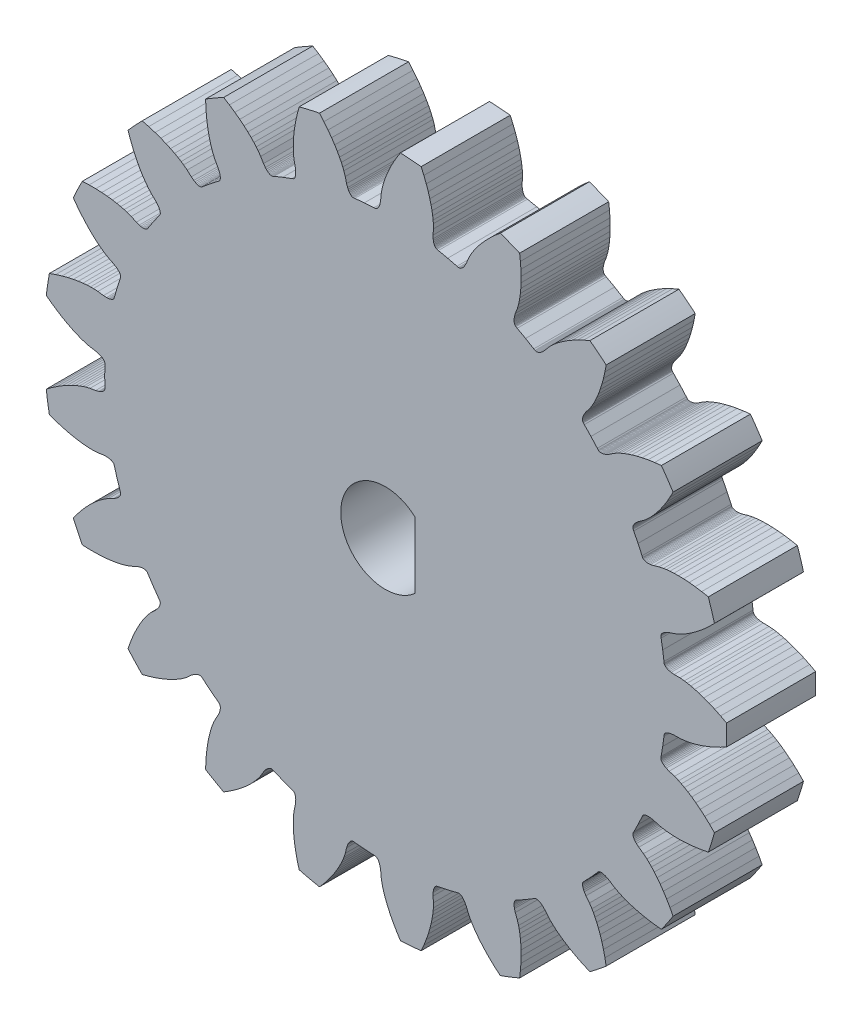
SolidWorks part; units mm, degrees
ref_plane "Front Plane" through (0, 0, 0) normal (0, 0, 1) x (1, 0, 0)
ref_plane "Top Plane" through (0, 0, 0) normal (0, 1, 0) x (1, 0, 0)
ref_plane "Right Plane" through (0, 0, 0) normal (1, 0, 0) x (0, 0, -1)
sketch "Model" plane through (0, 0, 0) normal (0, 0, 1) x (1, 0, 0)
  line L0 (10.9267, 2.8918) -> (10.7633, 2.7404)
  line L1 (10.7633, 2.7404) -> (10.6079, 2.6079)
  line L2 (10.6079, 2.6079) -> (10.4602, 2.4924)
  line L3 (10.4602, 2.4924) -> (10.3215, 2.3929)
  line L4 (10.3215, 2.3929) -> (10.1944, 2.3095)
  line L5 (10.1944, 2.3095) -> (10.0772, 2.2395)
  line L6 (10.0772, 2.2395) -> (9.9721, 2.1826)
  line L7 (9.9721, 2.1826) -> (9.8817, 2.1384)
  line L8 (9.8817, 2.1384) -> (9.7426, 2.0805)
  line L9 (9.7426, 2.0805) -> (9.5615, 2.023)
  line L10 (9.5615, 2.023) -> (9.4651, 1.9818)
  line L11 (9.4651, 1.9818) -> (9.4245, 1.9597)
  line L12 (9.4245, 1.9597) -> (9.3889, 1.9369)
  line L13 (9.3889, 1.9369) -> (9.3585, 1.9135)
  line L14 (9.3585, 1.9135) -> (9.3331, 1.8898)
  line L15 (9.3331, 1.8898) -> (9.3128, 1.866)
  line L16 (9.3128, 1.866) -> (9.2976, 1.8422)
  line L17 (9.2976, 1.8422) -> (9.2875, 1.8187)
  line L18 (9.2875, 1.8187) -> (9.2824, 1.7958)
  line L19 (9.2824, 1.7958) -> (9.2824, 1.7734)
  line L20 (9.2824, 1.7734) -> (9.291, 1.7262)
  line L21 (9.291, 1.7262) -> (9.3445, 1.4084)
  line L22 (9.3445, 1.4084) -> (9.3871, 1.0891)
  line L23 (9.3871, 1.0891) -> (9.3927, 1.0414)
  line L24 (9.3927, 1.0414) -> (9.3994, 1.0201)
  line L25 (9.3994, 1.0201) -> (9.411, 0.9996)
  line L26 (9.411, 0.9996) -> (9.4276, 0.9802)
  line L27 (9.4276, 0.9802) -> (9.4491, 0.9619)
  line L28 (9.4491, 0.9619) -> (9.4755, 0.9451)
  line L29 (9.4755, 0.9451) -> (9.5067, 0.93)
  line L30 (9.5067, 0.93) -> (9.5427, 0.9166)
  line L31 (9.5427, 0.9166) -> (9.5834, 0.9053)
  line L32 (9.5834, 0.9053) -> (9.6287, 0.8961)
  line L33 (9.6287, 0.8961) -> (9.733, 0.8852)
  line L34 (9.733, 0.8852) -> (9.923, 0.8836)
  line L35 (9.923, 0.8836) -> (10.073, 0.8693)
  line L36 (10.073, 0.8693) -> (10.1724, 0.8537)
  line L37 (10.1724, 0.8537) -> (10.2896, 0.8303)
  line L38 (10.2896, 0.8303) -> (10.4222, 0.7979)
  line L39 (10.4222, 0.7979) -> (10.5682, 0.7558)
  line L40 (10.5682, 0.7558) -> (10.7301, 0.7016)
  line L41 (10.7301, 0.7016) -> (10.9053, 0.6347)
  line L42 (10.9053, 0.6347) -> (11.0929, 0.5539)
  line L43 (11.0929, 0.5539) -> (11.2936, 0.4574)
  line L44 (11.2936, 0.4574) -> (11.4947, 0.3502)
  line L45 (11.4947, -0.3502) -> (11.2936, -0.4574)
  line L46 (11.2936, -0.4574) -> (11.0929, -0.5539)
  line L47 (11.0929, -0.5539) -> (10.9053, -0.6347)
  line L48 (10.9053, -0.6347) -> (10.7301, -0.7016)
  line L49 (10.7301, -0.7016) -> (10.5682, -0.7558)
  line L50 (10.5682, -0.7558) -> (10.4222, -0.7979)
  line L51 (10.4222, -0.7979) -> (10.2896, -0.8303)
  line L52 (10.2896, -0.8303) -> (10.1724, -0.8537)
  line L53 (10.1724, -0.8537) -> (10.073, -0.8693)
  line L54 (10.073, -0.8693) -> (9.923, -0.8836)
  line L55 (9.923, -0.8836) -> (9.733, -0.8852)
  line L56 (9.733, -0.8852) -> (9.6287, -0.8961)
  line L57 (9.6287, -0.8961) -> (9.5834, -0.9053)
  line L58 (9.5834, -0.9053) -> (9.5427, -0.9166)
  line L59 (9.5427, -0.9166) -> (9.5067, -0.93)
  line L60 (9.5067, -0.93) -> (9.4755, -0.9451)
  line L61 (9.4755, -0.9451) -> (9.4491, -0.9619)
  line L62 (9.4491, -0.9619) -> (9.4276, -0.9802)
  line L63 (9.4276, -0.9802) -> (9.411, -0.9996)
  line L64 (9.411, -0.9996) -> (9.3994, -1.0201)
  line L65 (9.3994, -1.0201) -> (9.3927, -1.0414)
  line L66 (9.3927, -1.0414) -> (9.3871, -1.0891)
  line L67 (9.3871, -1.0891) -> (9.3445, -1.4084)
  line L68 (9.3445, -1.4084) -> (9.291, -1.7262)
  line L69 (9.291, -1.7262) -> (9.2824, -1.7734)
  line L70 (9.2824, -1.7734) -> (9.2824, -1.7958)
  line L71 (9.2824, -1.7958) -> (9.2875, -1.8187)
  line L72 (9.2875, -1.8187) -> (9.2976, -1.8422)
  line L73 (9.2976, -1.8422) -> (9.3128, -1.866)
  line L74 (9.3128, -1.866) -> (9.3331, -1.8898)
  line L75 (9.3331, -1.8898) -> (9.3585, -1.9135)
  line L76 (9.3585, -1.9135) -> (9.3889, -1.9369)
  line L77 (9.3889, -1.9369) -> (9.4245, -1.9597)
  line L78 (9.4245, -1.9597) -> (9.4651, -1.9818)
  line L79 (9.4651, -1.9818) -> (9.5615, -2.023)
  line L80 (9.5615, -2.023) -> (9.7426, -2.0805)
  line L81 (9.7426, -2.0805) -> (9.8817, -2.1384)
  line L82 (9.8817, -2.1384) -> (9.9721, -2.1826)
  line L83 (9.9721, -2.1826) -> (10.0772, -2.2395)
  line L84 (10.0772, -2.2395) -> (10.1944, -2.3095)
  line L85 (10.1944, -2.3095) -> (10.3215, -2.3929)
  line L86 (10.3215, -2.3929) -> (10.4602, -2.4924)
  line L87 (10.4602, -2.4924) -> (10.6079, -2.6079)
  line L88 (10.6079, -2.6079) -> (10.7633, -2.7404)
  line L89 (10.7633, -2.7404) -> (10.9267, -2.8918)
  line L90 (10.9267, -2.8918) -> (11.0872, -3.0535)
  line L91 (10.8808, -3.7227) -> (10.657, -3.7659)
  line L92 (10.657, -3.7659) -> (10.4368, -3.799)
  line L93 (10.4368, -3.799) -> (10.2338, -3.8209)
  line L94 (10.2338, -3.8209) -> (10.0466, -3.8332)
  line L95 (10.0466, -3.8332) -> (9.8759, -3.8372)
  line L96 (9.8759, -3.8372) -> (9.724, -3.8345)
  line L97 (9.724, -3.8345) -> (9.5877, -3.8263)
  line L98 (9.5877, -3.8263) -> (9.4689, -3.8142)
  line L99 (9.4689, -3.8142) -> (9.3693, -3.7997)
  line L100 (9.3693, -3.7997) -> (9.2217, -3.7692)
  line L101 (9.2217, -3.7692) -> (9.0397, -3.7147)
  line L102 (9.0397, -3.7147) -> (8.9368, -3.6944)
  line L103 (8.9368, -3.6944) -> (8.8908, -3.6898)
  line L104 (8.8908, -3.6898) -> (8.8486, -3.6886)
  line L105 (8.8486, -3.6886) -> (8.8103, -3.6908)
  line L106 (8.8103, -3.6908) -> (8.7759, -3.6961)
  line L107 (8.7759, -3.6961) -> (8.7458, -3.7044)
  line L108 (8.7458, -3.7044) -> (8.7198, -3.7154)
  line L109 (8.7198, -3.7154) -> (8.6982, -3.7291)
  line L110 (8.6982, -3.7291) -> (8.6811, -3.7453)
  line L111 (8.6811, -3.7453) -> (8.6685, -3.7637)
  line L112 (8.6685, -3.7637) -> (8.649, -3.8076)
  line L113 (8.649, -3.8076) -> (8.5142, -4.1002)
  line L114 (8.5142, -4.1002) -> (8.3695, -4.3881)
  line L115 (8.3695, -4.3881) -> (8.3473, -4.4307)
  line L116 (8.3473, -4.4307) -> (8.3407, -4.452)
  line L117 (8.3407, -4.452) -> (8.3388, -4.4755)
  line L118 (8.3388, -4.4755) -> (8.3416, -4.5009)
  line L119 (8.3416, -4.5009) -> (8.3491, -4.5281)
  line L120 (8.3491, -4.5281) -> (8.3614, -4.5568)
  line L121 (8.3614, -4.5568) -> (8.3787, -4.587)
  line L122 (8.3787, -4.587) -> (8.4009, -4.6183)
  line L123 (8.4009, -4.6183) -> (8.4281, -4.6506)
  line L124 (8.4281, -4.6506) -> (8.4604, -4.6837)
  line L125 (8.4604, -4.6837) -> (8.5404, -4.7514)
  line L126 (8.5404, -4.7514) -> (8.6965, -4.8598)
  line L127 (8.6965, -4.8598) -> (8.8124, -4.9561)
  line L128 (8.8124, -4.9561) -> (8.8858, -5.025)
  line L129 (8.8858, -5.025) -> (8.9694, -5.1103)
  line L130 (8.9694, -5.1103) -> (9.0607, -5.2117)
  line L131 (9.0607, -5.2117) -> (9.1576, -5.3289)
  line L132 (9.1576, -5.3289) -> (9.2609, -5.4648)
  line L133 (9.2609, -5.4648) -> (9.3679, -5.6188)
  line L134 (9.3679, -5.6188) -> (9.4774, -5.7912)
  line L135 (9.4774, -5.7912) -> (9.5889, -5.984)
  line L136 (9.5889, -5.984) -> (9.6946, -6.1858)
  line L137 (9.3001, -6.7645) -> (9.0736, -6.7398)
  line L138 (9.0736, -6.7398) -> (8.8533, -6.7065)
  line L139 (8.8533, -6.7065) -> (8.6529, -6.6676)
  line L140 (8.6529, -6.6676) -> (8.4704, -6.6242)
  line L141 (8.4704, -6.6242) -> (8.3061, -6.5777)
  line L142 (8.3061, -6.5777) -> (8.1617, -6.5303)
  line L143 (8.1617, -6.5303) -> (8.0339, -6.4824)
  line L144 (8.0339, -6.4824) -> (7.9239, -6.4357)
  line L145 (7.9239, -6.4357) -> (7.833, -6.3926)
  line L146 (7.833, -6.3926) -> (7.701, -6.3199)
  line L147 (7.701, -6.3199) -> (7.5431, -6.2141)
  line L148 (7.5431, -6.2141) -> (7.4508, -6.1645)
  line L149 (7.4508, -6.1645) -> (7.4082, -6.1465)
  line L150 (7.4082, -6.1465) -> (7.3682, -6.1329)
  line L151 (7.3682, -6.1329) -> (7.331, -6.1237)
  line L152 (7.331, -6.1237) -> (7.2966, -6.1186)
  line L153 (7.2966, -6.1186) -> (7.2653, -6.1177)
  line L154 (7.2653, -6.1177) -> (7.2373, -6.1206)
  line L155 (7.2373, -6.1206) -> (7.2126, -6.1273)
  line L156 (7.2126, -6.1273) -> (7.1915, -6.1377)
  line L157 (7.1915, -6.1377) -> (7.174, -6.1515)
  line L158 (7.174, -6.1515) -> (7.1425, -6.1878)
  line L159 (7.1425, -6.1878) -> (6.9273, -6.4276)
  line L160 (6.9273, -6.4276) -> (6.7042, -6.6601)
  line L161 (6.7042, -6.6601) -> (6.6705, -6.6942)
  line L162 (6.6705, -6.6942) -> (6.6579, -6.7127)
  line L163 (6.6579, -6.7127) -> (6.6492, -6.7346)
  line L164 (6.6492, -6.7346) -> (6.6443, -6.7597)
  line L165 (6.6443, -6.7597) -> (6.6435, -6.7879)
  line L166 (6.6435, -6.7879) -> (6.6468, -6.819)
  line L167 (6.6468, -6.819) -> (6.6544, -6.8528)
  line L168 (6.6544, -6.8528) -> (6.6664, -6.8893)
  line L169 (6.6664, -6.8893) -> (6.6829, -6.9282)
  line L170 (6.6829, -6.9282) -> (6.704, -6.9693)
  line L171 (6.704, -6.9693) -> (6.7605, -7.0577)
  line L172 (6.7605, -7.0577) -> (6.8777, -7.2072)
  line L173 (6.8777, -7.2072) -> (6.9601, -7.3334)
  line L174 (6.9601, -7.3334) -> (7.0099, -7.4208)
  line L175 (7.0099, -7.4208) -> (7.0646, -7.527)
  line L176 (7.0646, -7.527) -> (7.122, -7.6509)
  line L177 (7.122, -7.6509) -> (7.1801, -7.7914)
  line L178 (7.1801, -7.7914) -> (7.2387, -7.9517)
  line L179 (7.2387, -7.9517) -> (7.2956, -8.1304)
  line L180 (7.2956, -8.1304) -> (7.3494, -8.3274)
  line L181 (7.3494, -8.3274) -> (7.399, -8.5445)
  line L182 (7.399, -8.5445) -> (7.4406, -8.7685)
  line L183 (6.893, -9.2052) -> (6.6839, -9.1149)
  line L184 (6.6839, -9.1149) -> (6.4832, -9.0181)
  line L185 (6.4832, -9.0181) -> (6.3032, -8.9218)
  line L186 (6.3032, -8.9218) -> (6.1416, -8.8266)
  line L187 (6.1416, -8.8266) -> (5.9983, -8.7338)
  line L188 (5.9983, -8.7338) -> (5.8743, -8.6459)
  line L189 (5.8743, -8.6459) -> (5.7663, -8.5624)
  line L190 (5.7663, -8.5624) -> (5.6749, -8.4854)
  line L191 (5.6749, -8.4854) -> (5.6008, -8.4174)
  line L192 (5.6008, -8.4174) -> (5.4961, -8.309)
  line L193 (5.4961, -8.309) -> (5.3764, -8.1614)
  line L194 (5.3764, -8.1614) -> (5.3028, -8.0868)
  line L195 (5.3028, -8.0868) -> (5.2674, -8.057)
  line L196 (5.2674, -8.057) -> (5.2332, -8.0323)
  line L197 (5.2332, -8.0323) -> (5.2003, -8.0125)
  line L198 (5.2003, -8.0125) -> (5.1689, -7.9975)
  line L199 (5.1689, -7.9975) -> (5.1394, -7.9874)
  line L200 (5.1394, -7.9874) -> (5.1117, -7.9819)
  line L201 (5.1117, -7.9819) -> (5.0861, -7.981)
  line L202 (5.0861, -7.981) -> (5.0629, -7.9847)
  line L203 (5.0629, -7.9847) -> (5.0421, -7.9928)
  line L204 (5.0421, -7.9928) -> (5.0013, -8.0181)
  line L205 (5.0013, -8.0181) -> (4.725, -8.1839)
  line L206 (4.725, -8.1839) -> (4.4433, -8.3403)
  line L207 (4.4433, -8.3403) -> (4.4009, -8.363)
  line L208 (4.4009, -8.363) -> (4.3835, -8.3769)
  line L209 (4.3835, -8.3769) -> (4.3687, -8.3952)
  line L210 (4.3687, -8.3952) -> (4.3567, -8.4178)
  line L211 (4.3567, -8.4178) -> (4.3476, -8.4445)
  line L212 (4.3476, -8.4445) -> (4.3416, -8.4752)
  line L213 (4.3416, -8.4752) -> (4.3389, -8.5098)
  line L214 (4.3389, -8.5098) -> (4.3396, -8.5482)
  line L215 (4.3396, -8.5482) -> (4.3439, -8.5902)
  line L216 (4.3439, -8.5902) -> (4.3519, -8.6358)
  line L217 (4.3519, -8.6358) -> (4.3798, -8.7368)
  line L218 (4.3798, -8.7368) -> (4.4478, -8.9142)
  line L219 (4.4478, -8.9142) -> (4.4893, -9.0591)
  line L220 (4.4893, -9.0591) -> (4.5111, -9.1574)
  line L221 (4.5111, -9.1574) -> (4.5321, -9.275)
  line L222 (4.5321, -9.275) -> (4.5504, -9.4102)
  line L223 (4.5504, -9.4102) -> (4.5645, -9.5616)
  line L224 (4.5645, -9.5616) -> (4.5732, -9.7321)
  line L225 (4.5732, -9.7321) -> (4.575, -9.9196)
  line L226 (4.575, -9.9196) -> (4.5683, -10.1237)
  line L227 (4.5683, -10.1237) -> (4.5518, -10.3458)
  line L228 (4.5518, -10.3458) -> (4.5254, -10.5721)
  line L229 (3.8735, -10.828) -> (3.7003, -10.68)
  line L230 (3.7003, -10.68) -> (3.537, -10.5284)
  line L231 (3.537, -10.5284) -> (3.3934, -10.3834)
  line L232 (3.3934, -10.3834) -> (3.2671, -10.2447)
  line L233 (3.2671, -10.2447) -> (3.1575, -10.1138)
  line L234 (3.1575, -10.1138) -> (3.0649, -9.9933)
  line L235 (3.0649, -9.9933) -> (2.9863, -9.8817)
  line L236 (2.9863, -9.8817) -> (2.9217, -9.7812)
  line L237 (2.9217, -9.7812) -> (2.8709, -9.6943)
  line L238 (2.8709, -9.6943) -> (2.8028, -9.5598)
  line L239 (2.8028, -9.5598) -> (2.7319, -9.3836)
  line L240 (2.7319, -9.3836) -> (2.6836, -9.2905)
  line L241 (2.6836, -9.2905) -> (2.6585, -9.2517)
  line L242 (2.6585, -9.2517) -> (2.6331, -9.2179)
  line L243 (2.6331, -9.2179) -> (2.6075, -9.1893)
  line L244 (2.6075, -9.1893) -> (2.582, -9.1658)
  line L245 (2.582, -9.1658) -> (2.5567, -9.1474)
  line L246 (2.5567, -9.1474) -> (2.5319, -9.134)
  line L247 (2.5319, -9.134) -> (2.5077, -9.1256)
  line L248 (2.5077, -9.1256) -> (2.4844, -9.1223)
  line L249 (2.4844, -9.1223) -> (2.4622, -9.1239)
  line L250 (2.4622, -9.1239) -> (2.4157, -9.1361)
  line L251 (2.4157, -9.1361) -> (2.1028, -9.2131)
  line L252 (2.1028, -9.2131) -> (1.7875, -9.2794)
  line L253 (1.7875, -9.2794) -> (1.7404, -9.2886)
  line L254 (1.7404, -9.2886) -> (1.7196, -9.2968)
  line L255 (1.7196, -9.2968) -> (1.7001, -9.31)
  line L256 (1.7001, -9.31) -> (1.6819, -9.328)
  line L257 (1.6819, -9.328) -> (1.6654, -9.3508)
  line L258 (1.6654, -9.3508) -> (1.6506, -9.3784)
  line L259 (1.6506, -9.3784) -> (1.6378, -9.4106)
  line L260 (1.6378, -9.4106) -> (1.6272, -9.4475)
  line L261 (1.6272, -9.4475) -> (1.6189, -9.489)
  line L262 (1.6189, -9.489) -> (1.6132, -9.5348)
  line L263 (1.6132, -9.5348) -> (1.61, -9.6396)
  line L264 (1.61, -9.6396) -> (1.6227, -9.8292)
  line L265 (1.6227, -9.8292) -> (1.6196, -9.9799)
  line L266 (1.6196, -9.9799) -> (1.6115, -10.0802)
  line L267 (1.6115, -10.0802) -> (1.5969, -10.1988)
  line L268 (1.5969, -10.1988) -> (1.5746, -10.3334)
  line L269 (1.5746, -10.3334) -> (1.5434, -10.4822)
  line L270 (1.5434, -10.4822) -> (1.5015, -10.6477)
  line L271 (1.5015, -10.6477) -> (1.4479, -10.8274)
  line L272 (1.4479, -10.8274) -> (1.3814, -11.0205)
  line L273 (1.3814, -11.0205) -> (1.3001, -11.2278)
  line L274 (1.3001, -11.2278) -> (1.2082, -11.4363)
  line L275 (0.5098, -11.4887) -> (0.3879, -11.2962)
  line L276 (0.3879, -11.2962) -> (0.2766, -11.1032)
  line L277 (0.2766, -11.1032) -> (0.1821, -10.9223)
  line L278 (0.1821, -10.9223) -> (0.1022, -10.7526)
  line L279 (0.1022, -10.7526) -> (0.0361, -10.5952)
  line L280 (0.0361, -10.5952) -> (-0.0169, -10.4527)
  line L281 (-0.0169, -10.4527) -> (-0.059, -10.3229)
  line L282 (-0.059, -10.3229) -> (-0.0911, -10.2078)
  line L283 (-0.0911, -10.2078) -> (-0.1141, -10.1098)
  line L284 (-0.1141, -10.1098) -> (-0.1396, -9.9613)
  line L285 (-0.1396, -9.9613) -> (-0.1553, -9.7719)
  line L286 (-0.1553, -9.7719) -> (-0.174, -9.6688)
  line L287 (-0.174, -9.6688) -> (-0.1866, -9.6243)
  line L288 (-0.1866, -9.6243) -> (-0.2009, -9.5845)
  line L289 (-0.2009, -9.5845) -> (-0.2169, -9.5496)
  line L290 (-0.2169, -9.5496) -> (-0.2344, -9.5196)
  line L291 (-0.2344, -9.5196) -> (-0.2531, -9.4946)
  line L292 (-0.2531, -9.4946) -> (-0.2729, -9.4745)
  line L293 (-0.2729, -9.4745) -> (-0.2935, -9.4594)
  line L294 (-0.2935, -9.4594) -> (-0.3148, -9.4493)
  line L295 (-0.3148, -9.4493) -> (-0.3366, -9.4443)
  line L296 (-0.3366, -9.4443) -> (-0.3845, -9.4422)
  line L297 (-0.3845, -9.4422) -> (-0.7062, -9.4236)
  line L298 (-0.7062, -9.4236) -> (-1.027, -9.3941)
  line L299 (-1.027, -9.3941) -> (-1.0748, -9.389)
  line L300 (-1.0748, -9.389) -> (-1.0971, -9.3907)
  line L301 (-1.0971, -9.3907) -> (-1.1196, -9.3975)
  line L302 (-1.1196, -9.3975) -> (-1.1423, -9.4093)
  line L303 (-1.1423, -9.4093) -> (-1.1648, -9.4262)
  line L304 (-1.1648, -9.4262) -> (-1.1871, -9.4482)
  line L305 (-1.1871, -9.4482) -> (-1.2088, -9.4753)
  line L306 (-1.2088, -9.4753) -> (-1.2298, -9.5074)
  line L307 (-1.2298, -9.5074) -> (-1.25, -9.5446)
  line L308 (-1.25, -9.5446) -> (-1.269, -9.5867)
  line L309 (-1.269, -9.5867) -> (-1.3028, -9.6859)
  line L310 (-1.3028, -9.6859) -> (-1.3466, -9.8708)
  line L311 (-1.3466, -9.8708) -> (-1.394, -10.0139)
  line L312 (-1.394, -10.0139) -> (-1.4313, -10.1074)
  line L313 (-1.4313, -10.1074) -> (-1.4802, -10.2164)
  line L314 (-1.4802, -10.2164) -> (-1.5412, -10.3384)
  line L315 (-1.5412, -10.3384) -> (-1.6148, -10.4714)
  line L316 (-1.6148, -10.4714) -> (-1.7037, -10.6172)
  line L317 (-1.7037, -10.6172) -> (-1.8079, -10.7731)
  line L318 (-1.8079, -10.7731) -> (-1.9284, -10.938)
  line L319 (-1.9284, -10.938) -> (-2.0672, -11.1122)
  line L320 (-2.0672, -11.1122) -> (-2.2164, -11.2844)
  line L321 (-2.8992, -11.1285) -> (-2.959, -10.9087)
  line L322 (-2.959, -10.9087) -> (-3.0084, -10.6915)
  line L323 (-3.0084, -10.6915) -> (-3.0454, -10.4907)
  line L324 (-3.0454, -10.4907) -> (-3.0717, -10.305)
  line L325 (-3.0717, -10.305) -> (-3.0885, -10.1351)
  line L326 (-3.0885, -10.1351) -> (-3.0971, -9.9833)
  line L327 (-3.0971, -9.9833) -> (-3.0991, -9.8468)
  line L328 (-3.0991, -9.8468) -> (-3.0959, -9.7274)
  line L329 (-3.0959, -9.7274) -> (-3.089, -9.627)
  line L330 (-3.089, -9.627) -> (-3.0695, -9.4776)
  line L331 (-3.0695, -9.4776) -> (-3.0288, -9.292)
  line L332 (-3.0288, -9.292) -> (-3.0162, -9.1879)
  line L333 (-3.0162, -9.1879) -> (-3.0151, -9.1417)
  line L334 (-3.0151, -9.1417) -> (-3.0171, -9.0995)
  line L335 (-3.0171, -9.0995) -> (-3.0221, -9.0614)
  line L336 (-3.0221, -9.0614) -> (-3.0299, -9.0276)
  line L337 (-3.0299, -9.0276) -> (-3.0404, -8.9981)
  line L338 (-3.0404, -8.9981) -> (-3.0534, -8.9731)
  line L339 (-3.0534, -8.9731) -> (-3.0687, -8.9526)
  line L340 (-3.0687, -8.9526) -> (-3.0861, -8.9367)
  line L341 (-3.0861, -8.9367) -> (-3.1054, -8.9255)
  line L342 (-3.1054, -8.9255) -> (-3.1506, -8.9094)
  line L343 (-3.1506, -8.9094) -> (-3.4525, -8.7968)
  line L344 (-3.4525, -8.7968) -> (-3.7504, -8.674)
  line L345 (-3.7504, -8.674) -> (-3.7945, -8.655)
  line L346 (-3.7945, -8.655) -> (-3.8163, -8.6501)
  line L347 (-3.8163, -8.6501) -> (-3.8398, -8.65)
  line L348 (-3.8398, -8.65) -> (-3.8649, -8.6546)
  line L349 (-3.8649, -8.6546) -> (-3.8915, -8.6641)
  line L350 (-3.8915, -8.6641) -> (-3.9192, -8.6786)
  line L351 (-3.9192, -8.6786) -> (-3.948, -8.698)
  line L352 (-3.948, -8.698) -> (-3.9776, -8.7225)
  line L353 (-3.9776, -8.7225) -> (-4.0077, -8.7521)
  line L354 (-4.0077, -8.7521) -> (-4.0383, -8.7868)
  line L355 (-4.0383, -8.7868) -> (-4.0999, -8.8716)
  line L356 (-4.0999, -8.8716) -> (-4.1963, -9.0353)
  line L357 (-4.1963, -9.0353) -> (-4.2837, -9.1581)
  line L358 (-4.2837, -9.1581) -> (-4.3469, -9.2364)
  line L359 (-4.3469, -9.2364) -> (-4.4257, -9.3262)
  line L360 (-4.4257, -9.3262) -> (-4.5201, -9.4249)
  line L361 (-4.5201, -9.4249) -> (-4.6296, -9.5302)
  line L362 (-4.6296, -9.5302) -> (-4.7575, -9.6434)
  line L363 (-4.7575, -9.6434) -> (-4.903, -9.7616)
  line L364 (-4.903, -9.7616) -> (-5.0667, -9.8837)
  line L365 (-5.0667, -9.8837) -> (-5.2507, -10.0092)
  line L366 (-5.2507, -10.0092) -> (-5.4441, -10.1297)
  line L367 (-6.0506, -9.7796) -> (-6.0429, -9.5519)
  line L368 (-6.0429, -9.5519) -> (-6.0262, -9.3297)
  line L369 (-6.0262, -9.3297) -> (-6.0023, -9.127)
  line L370 (-6.0023, -9.127) -> (-5.9727, -8.9418)
  line L371 (-5.9727, -8.9418) -> (-5.9386, -8.7745)
  line L372 (-5.9386, -8.7745) -> (-5.9021, -8.6269)
  line L373 (-5.9021, -8.6269) -> (-5.8639, -8.4959)
  line L374 (-5.8639, -8.4959) -> (-5.8256, -8.3827)
  line L375 (-5.8256, -8.3827) -> (-5.7893, -8.2888)
  line L376 (-5.7893, -8.2888) -> (-5.7267, -8.1517)
  line L377 (-5.7267, -8.1517) -> (-5.6331, -7.9864)
  line L378 (-5.6331, -7.9864) -> (-5.5904, -7.8907)
  line L379 (-5.5904, -7.8907) -> (-5.5757, -7.8468)
  line L380 (-5.5757, -7.8468) -> (-5.5652, -7.8059)
  line L381 (-5.5652, -7.8059) -> (-5.5587, -7.7681)
  line L382 (-5.5587, -7.7681) -> (-5.5563, -7.7334)
  line L383 (-5.5563, -7.7334) -> (-5.5576, -7.7022)
  line L384 (-5.5576, -7.7022) -> (-5.5626, -7.6744)
  line L385 (-5.5626, -7.6744) -> (-5.5712, -7.6504)
  line L386 (-5.5712, -7.6504) -> (-5.5831, -7.63)
  line L387 (-5.5831, -7.63) -> (-5.5982, -7.6136)
  line L388 (-5.5982, -7.6136) -> (-5.6367, -7.5849)
  line L389 (-5.6367, -7.5849) -> (-5.892, -7.3883)
  line L390 (-5.892, -7.3883) -> (-6.1404, -7.1832)
  line L391 (-6.1404, -7.1832) -> (-6.177, -7.1521)
  line L392 (-6.177, -7.1521) -> (-6.1964, -7.141)
  line L393 (-6.1964, -7.141) -> (-6.2188, -7.1339)
  line L394 (-6.2188, -7.1339) -> (-6.2442, -7.1309)
  line L395 (-6.2442, -7.1309) -> (-6.2724, -7.1322)
  line L396 (-6.2724, -7.1322) -> (-6.3032, -7.1378)
  line L397 (-6.3032, -7.1378) -> (-6.3364, -7.1479)
  line L398 (-6.3364, -7.1479) -> (-6.3719, -7.1626)
  line L399 (-6.3719, -7.1626) -> (-6.4094, -7.182)
  line L400 (-6.4094, -7.182) -> (-6.4489, -7.2061)
  line L401 (-6.4489, -7.2061) -> (-6.5327, -7.269)
  line L402 (-6.5327, -7.269) -> (-6.6731, -7.3971)
  line L403 (-6.6731, -7.3971) -> (-6.7928, -7.4886)
  line L404 (-6.7928, -7.4886) -> (-6.8762, -7.5448)
  line L405 (-6.8762, -7.5448) -> (-6.978, -7.6074)
  line L406 (-6.978, -7.6074) -> (-7.0973, -7.6738)
  line L407 (-7.0973, -7.6738) -> (-7.233, -7.7422)
  line L408 (-7.233, -7.7422) -> (-7.3886, -7.8126)
  line L409 (-7.3886, -7.8126) -> (-7.5625, -7.8828)
  line L410 (-7.5625, -7.8828) -> (-7.7549, -7.9511)
  line L411 (-7.7549, -7.9511) -> (-7.9677, -8.0169)
  line L412 (-7.9677, -8.0169) -> (-8.188, -8.075)
  line L413 (-8.6644, -7.5617) -> (-8.5899, -7.3463)
  line L414 (-8.5899, -7.3463) -> (-8.5084, -7.139)
  line L415 (-8.5084, -7.139) -> (-8.4259, -6.9523)
  line L416 (-8.4259, -6.9523) -> (-8.3429, -6.7841)
  line L417 (-8.3429, -6.7841) -> (-8.2611, -6.6342)
  line L418 (-8.2611, -6.6342) -> (-8.1827, -6.504)
  line L419 (-8.1827, -6.504) -> (-8.1076, -6.39)
  line L420 (-8.1076, -6.39) -> (-8.0376, -6.2932)
  line L421 (-8.0376, -6.2932) -> (-7.9753, -6.2141)
  line L422 (-7.9753, -6.2141) -> (-7.875, -6.1016)
  line L423 (-7.875, -6.1016) -> (-7.7368, -5.9712)
  line L424 (-7.7368, -5.9712) -> (-7.6679, -5.8923)
  line L425 (-7.6679, -5.8923) -> (-7.6409, -5.8548)
  line L426 (-7.6409, -5.8548) -> (-7.6188, -5.8188)
  line L427 (-7.6188, -5.8188) -> (-7.6015, -5.7845)
  line L428 (-7.6015, -5.7845) -> (-7.5889, -5.7521)
  line L429 (-7.5889, -5.7521) -> (-7.581, -5.7219)
  line L430 (-7.581, -5.7219) -> (-7.5776, -5.6939)
  line L431 (-7.5776, -5.6939) -> (-7.5786, -5.6683)
  line L432 (-7.5786, -5.6683) -> (-7.584, -5.6454)
  line L433 (-7.584, -5.6454) -> (-7.5937, -5.6253)
  line L434 (-7.5937, -5.6253) -> (-7.622, -5.5865)
  line L435 (-7.622, -5.5865) -> (-7.808, -5.3234)
  line L436 (-7.808, -5.3234) -> (-7.9849, -5.0541)
  line L437 (-7.9849, -5.0541) -> (-8.0107, -5.0136)
  line L438 (-8.0107, -5.0136) -> (-8.0259, -4.9973)
  line L439 (-8.0259, -4.9973) -> (-8.0453, -4.9839)
  line L440 (-8.0453, -4.9839) -> (-8.0687, -4.9736)
  line L441 (-8.0687, -4.9736) -> (-8.096, -4.9665)
  line L442 (-8.096, -4.9665) -> (-8.127, -4.9628)
  line L443 (-8.127, -4.9628) -> (-8.1618, -4.9627)
  line L444 (-8.1618, -4.9627) -> (-8.2, -4.9663)
  line L445 (-8.2, -4.9663) -> (-8.2416, -4.9737)
  line L446 (-8.2416, -4.9737) -> (-8.2864, -4.9851)
  line L447 (-8.2864, -4.9851) -> (-8.3851, -5.0205)
  line L448 (-8.3851, -5.0205) -> (-8.5569, -5.1015)
  line L449 (-8.5569, -5.1015) -> (-8.6983, -5.1537)
  line L450 (-8.6983, -5.1537) -> (-8.7946, -5.1828)
  line L451 (-8.7946, -5.1828) -> (-8.9103, -5.2126)
  line L452 (-8.9103, -5.2126) -> (-9.0439, -5.2409)
  line L453 (-9.0439, -5.2409) -> (-9.1937, -5.2663)
  line L454 (-9.1937, -5.2663) -> (-9.3631, -5.2877)
  line L455 (-9.3631, -5.2877) -> (-9.55, -5.3035)
  line L456 (-9.55, -5.3035) -> (-9.754, -5.3121)
  line L457 (-9.754, -5.3121) -> (-9.9767, -5.3122)
  line L458 (-9.9767, -5.3122) -> (-10.2044, -5.3028)
  line L459 (-10.5083, -4.6718) -> (-10.3736, -4.488)
  line L460 (-10.3736, -4.488) -> (-10.2347, -4.3139)
  line L461 (-10.2347, -4.3139) -> (-10.1007, -4.1598)
  line L462 (-10.1007, -4.1598) -> (-9.9719, -4.0235)
  line L463 (-9.9719, -4.0235) -> (-9.8496, -3.9045)
  line L464 (-9.8496, -3.9045) -> (-9.7363, -3.8031)
  line L465 (-9.7363, -3.8031) -> (-9.6309, -3.7164)
  line L466 (-9.6309, -3.7164) -> (-9.5355, -3.6445)
  line L467 (-9.5355, -3.6445) -> (-9.4526, -3.5873)
  line L468 (-9.4526, -3.5873) -> (-9.3237, -3.5093)
  line L469 (-9.3237, -3.5093) -> (-9.1532, -3.4255)
  line L470 (-9.1532, -3.4255) -> (-9.064, -3.3704)
  line L471 (-9.064, -3.3704) -> (-9.0271, -3.3425)
  line L472 (-9.0271, -3.3425) -> (-8.9954, -3.3146)
  line L473 (-8.9954, -3.3146) -> (-8.9688, -3.2869)
  line L474 (-8.9688, -3.2869) -> (-8.9472, -3.2597)
  line L475 (-8.9472, -3.2597) -> (-8.9307, -3.2331)
  line L476 (-8.9307, -3.2331) -> (-8.9192, -3.2074)
  line L477 (-8.9192, -3.2074) -> (-8.9127, -3.1827)
  line L478 (-8.9127, -3.1827) -> (-8.9111, -3.1592)
  line L479 (-8.9111, -3.1592) -> (-8.9144, -3.1371)
  line L480 (-8.9144, -3.1371) -> (-8.93, -3.0917)
  line L481 (-8.93, -3.0917) -> (-9.0302, -2.7854)
  line L482 (-9.0302, -2.7854) -> (-9.1199, -2.476)
  line L483 (-9.1199, -2.476) -> (-9.1326, -2.4297)
  line L484 (-9.1326, -2.4297) -> (-9.1423, -2.4096)
  line L485 (-9.1423, -2.4096) -> (-9.1569, -2.3911)
  line L486 (-9.1569, -2.3911) -> (-9.1762, -2.3743)
  line L487 (-9.1762, -2.3743) -> (-9.2002, -2.3595)
  line L488 (-9.2002, -2.3595) -> (-9.2288, -2.3468)
  line L489 (-9.2288, -2.3468) -> (-9.2619, -2.3365)
  line L490 (-9.2619, -2.3365) -> (-9.2995, -2.3286)
  line L491 (-9.2995, -2.3286) -> (-9.3414, -2.3235)
  line L492 (-9.3414, -2.3235) -> (-9.3876, -2.3212)
  line L493 (-9.3876, -2.3212) -> (-9.4923, -2.3259)
  line L494 (-9.4923, -2.3259) -> (-9.6804, -2.3527)
  line L495 (-9.6804, -2.3527) -> (-9.8309, -2.3609)
  line L496 (-9.8309, -2.3609) -> (-9.9316, -2.3603)
  line L497 (-9.9316, -2.3603) -> (-10.0509, -2.3546)
  line L498 (-10.0509, -2.3546) -> (-10.1869, -2.3424)
  line L499 (-10.1869, -2.3424) -> (-10.3375, -2.3224)
  line L500 (-10.3375, -2.3224) -> (-10.5057, -2.293)
  line L501 (-10.5057, -2.293) -> (-10.6889, -2.2529)
  line L502 (-10.6889, -2.2529) -> (-10.8864, -2.2011)
  line L503 (-10.8864, -2.2011) -> (-11.0993, -2.1355)
  line L504 (-11.0993, -2.1355) -> (-11.3141, -2.0595)
  line L505 (-11.4185, -1.3669) -> (-11.2356, -1.231)
  line L506 (-11.2356, -1.231) -> (-11.0515, -1.1056)
  line L507 (-11.0515, -1.1056) -> (-10.8781, -0.9978)
  line L508 (-10.8781, -0.9978) -> (-10.7149, -0.9055)
  line L509 (-10.7149, -0.9055) -> (-10.5628, -0.8278)
  line L510 (-10.5628, -0.8278) -> (-10.4247, -0.7643)
  line L511 (-10.4247, -0.7643) -> (-10.2984, -0.7125)
  line L512 (-10.2984, -0.7125) -> (-10.1861, -0.6719)
  line L513 (-10.1861, -0.6719) -> (-10.0901, -0.6417)
  line L514 (-10.0901, -0.6417) -> (-9.9438, -0.6052)
  line L515 (-9.9438, -0.6052) -> (-9.7562, -0.5753)
  line L516 (-9.7562, -0.5753) -> (-9.6547, -0.549)
  line L517 (-9.6547, -0.549) -> (-9.6113, -0.5332)
  line L518 (-9.6113, -0.5332) -> (-9.5727, -0.5159)
  line L519 (-9.5727, -0.5159) -> (-9.5391, -0.4973)
  line L520 (-9.5391, -0.4973) -> (-9.5105, -0.4777)
  line L521 (-9.5105, -0.4777) -> (-9.4869, -0.4571)
  line L522 (-9.4869, -0.4571) -> (-9.4684, -0.4359)
  line L523 (-9.4684, -0.4359) -> (-9.4549, -0.4142)
  line L524 (-9.4549, -0.4142) -> (-9.4464, -0.3922)
  line L525 (-9.4464, -0.3922) -> (-9.443, -0.3702)
  line L526 (-9.443, -0.3702) -> (-9.4445, -0.3221)
  line L527 (-9.4445, -0.3221) -> (-9.45, 0)
  line L528 (-9.45, 0) -> (-9.4445, 0.3221)
  line L529 (-9.4445, 0.3221) -> (-9.443, 0.3702)
  line L530 (-9.443, 0.3702) -> (-9.4464, 0.3922)
  line L531 (-9.4464, 0.3922) -> (-9.4549, 0.4142)
  line L532 (-9.4549, 0.4142) -> (-9.4684, 0.4359)
  line L533 (-9.4684, 0.4359) -> (-9.4869, 0.4571)
  line L534 (-9.4869, 0.4571) -> (-9.5105, 0.4777)
  line L535 (-9.5105, 0.4777) -> (-9.5391, 0.4973)
  line L536 (-9.5391, 0.4973) -> (-9.5727, 0.5159)
  line L537 (-9.5727, 0.5159) -> (-9.6113, 0.5332)
  line L538 (-9.6113, 0.5332) -> (-9.6547, 0.549)
  line L539 (-9.6547, 0.549) -> (-9.7562, 0.5753)
  line L540 (-9.7562, 0.5753) -> (-9.9438, 0.6052)
  line L541 (-9.9438, 0.6052) -> (-10.0901, 0.6417)
  line L542 (-10.0901, 0.6417) -> (-10.1861, 0.6719)
  line L543 (-10.1861, 0.6719) -> (-10.2984, 0.7125)
  line L544 (-10.2984, 0.7125) -> (-10.4247, 0.7643)
  line L545 (-10.4247, 0.7643) -> (-10.5628, 0.8278)
  line L546 (-10.5628, 0.8278) -> (-10.7149, 0.9055)
  line L547 (-10.7149, 0.9055) -> (-10.8781, 0.9978)
  line L548 (-10.8781, 0.9978) -> (-11.0515, 1.1056)
  line L549 (-11.0515, 1.1056) -> (-11.2356, 1.231)
  line L550 (-11.2356, 1.231) -> (-11.4185, 1.3669)
  line L551 (-11.3141, 2.0595) -> (-11.0993, 2.1355)
  line L552 (-11.0993, 2.1355) -> (-10.8864, 2.2011)
  line L553 (-10.8864, 2.2011) -> (-10.6889, 2.2529)
  line L554 (-10.6889, 2.2529) -> (-10.5057, 2.293)
  line L555 (-10.5057, 2.293) -> (-10.3375, 2.3224)
  line L556 (-10.3375, 2.3224) -> (-10.1869, 2.3424)
  line L557 (-10.1869, 2.3424) -> (-10.0509, 2.3546)
  line L558 (-10.0509, 2.3546) -> (-9.9316, 2.3603)
  line L559 (-9.9316, 2.3603) -> (-9.8309, 2.3609)
  line L560 (-9.8309, 2.3609) -> (-9.6804, 2.3527)
  line L561 (-9.6804, 2.3527) -> (-9.4923, 2.3259)
  line L562 (-9.4923, 2.3259) -> (-9.3876, 2.3212)
  line L563 (-9.3876, 2.3212) -> (-9.3414, 2.3235)
  line L564 (-9.3414, 2.3235) -> (-9.2995, 2.3286)
  line L565 (-9.2995, 2.3286) -> (-9.2619, 2.3365)
  line L566 (-9.2619, 2.3365) -> (-9.2288, 2.3468)
  line L567 (-9.2288, 2.3468) -> (-9.2002, 2.3595)
  line L568 (-9.2002, 2.3595) -> (-9.1762, 2.3743)
  line L569 (-9.1762, 2.3743) -> (-9.1569, 2.3911)
  line L570 (-9.1569, 2.3911) -> (-9.1423, 2.4096)
  line L571 (-9.1423, 2.4096) -> (-9.1326, 2.4297)
  line L572 (-9.1326, 2.4297) -> (-9.1199, 2.476)
  line L573 (-9.1199, 2.476) -> (-9.0302, 2.7854)
  line L574 (-9.0302, 2.7854) -> (-8.93, 3.0917)
  line L575 (-8.93, 3.0917) -> (-8.9144, 3.1371)
  line L576 (-8.9144, 3.1371) -> (-8.9111, 3.1592)
  line L577 (-8.9111, 3.1592) -> (-8.9127, 3.1827)
  line L578 (-8.9127, 3.1827) -> (-8.9192, 3.2074)
  line L579 (-8.9192, 3.2074) -> (-8.9307, 3.2331)
  line L580 (-8.9307, 3.2331) -> (-8.9472, 3.2597)
  line L581 (-8.9472, 3.2597) -> (-8.9688, 3.2869)
  line L582 (-8.9688, 3.2869) -> (-8.9954, 3.3146)
  line L583 (-8.9954, 3.3146) -> (-9.0271, 3.3425)
  line L584 (-9.0271, 3.3425) -> (-9.064, 3.3704)
  line L585 (-9.064, 3.3704) -> (-9.1532, 3.4255)
  line L586 (-9.1532, 3.4255) -> (-9.3237, 3.5093)
  line L587 (-9.3237, 3.5093) -> (-9.4526, 3.5873)
  line L588 (-9.4526, 3.5873) -> (-9.5355, 3.6445)
  line L589 (-9.5355, 3.6445) -> (-9.6309, 3.7164)
  line L590 (-9.6309, 3.7164) -> (-9.7363, 3.8031)
  line L591 (-9.7363, 3.8031) -> (-9.8496, 3.9045)
  line L592 (-9.8496, 3.9045) -> (-9.9719, 4.0235)
  line L593 (-9.9719, 4.0235) -> (-10.1007, 4.1598)
  line L594 (-10.1007, 4.1598) -> (-10.2347, 4.3139)
  line L595 (-10.2347, 4.3139) -> (-10.3736, 4.488)
  line L596 (-10.3736, 4.488) -> (-10.5083, 4.6718)
  line L597 (-10.2044, 5.3028) -> (-9.9767, 5.3122)
  line L598 (-9.9767, 5.3122) -> (-9.754, 5.3121)
  line L599 (-9.754, 5.3121) -> (-9.55, 5.3035)
  line L600 (-9.55, 5.3035) -> (-9.3631, 5.2877)
  line L601 (-9.3631, 5.2877) -> (-9.1937, 5.2663)
  line L602 (-9.1937, 5.2663) -> (-9.0439, 5.2409)
  line L603 (-9.0439, 5.2409) -> (-8.9103, 5.2126)
  line L604 (-8.9103, 5.2126) -> (-8.7946, 5.1828)
  line L605 (-8.7946, 5.1828) -> (-8.6983, 5.1537)
  line L606 (-8.6983, 5.1537) -> (-8.5569, 5.1015)
  line L607 (-8.5569, 5.1015) -> (-8.3851, 5.0205)
  line L608 (-8.3851, 5.0205) -> (-8.2864, 4.9851)
  line L609 (-8.2864, 4.9851) -> (-8.2416, 4.9737)
  line L610 (-8.2416, 4.9737) -> (-8.2, 4.9663)
  line L611 (-8.2, 4.9663) -> (-8.1618, 4.9627)
  line L612 (-8.1618, 4.9627) -> (-8.127, 4.9628)
  line L613 (-8.127, 4.9628) -> (-8.096, 4.9665)
  line L614 (-8.096, 4.9665) -> (-8.0687, 4.9736)
  line L615 (-8.0687, 4.9736) -> (-8.0453, 4.9839)
  line L616 (-8.0453, 4.9839) -> (-8.0259, 4.9973)
  line L617 (-8.0259, 4.9973) -> (-8.0107, 5.0136)
  line L618 (-8.0107, 5.0136) -> (-7.9849, 5.0541)
  line L619 (-7.9849, 5.0541) -> (-7.808, 5.3234)
  line L620 (-7.808, 5.3234) -> (-7.622, 5.5865)
  line L621 (-7.622, 5.5865) -> (-7.5937, 5.6253)
  line L622 (-7.5937, 5.6253) -> (-7.584, 5.6454)
  line L623 (-7.584, 5.6454) -> (-7.5786, 5.6683)
  line L624 (-7.5786, 5.6683) -> (-7.5776, 5.6939)
  line L625 (-7.5776, 5.6939) -> (-7.581, 5.7219)
  line L626 (-7.581, 5.7219) -> (-7.5889, 5.7521)
  line L627 (-7.5889, 5.7521) -> (-7.6015, 5.7845)
  line L628 (-7.6015, 5.7845) -> (-7.6188, 5.8188)
  line L629 (-7.6188, 5.8188) -> (-7.6409, 5.8548)
  line L630 (-7.6409, 5.8548) -> (-7.6679, 5.8923)
  line L631 (-7.6679, 5.8923) -> (-7.7368, 5.9712)
  line L632 (-7.7368, 5.9712) -> (-7.875, 6.1016)
  line L633 (-7.875, 6.1016) -> (-7.9753, 6.2141)
  line L634 (-7.9753, 6.2141) -> (-8.0376, 6.2932)
  line L635 (-8.0376, 6.2932) -> (-8.1076, 6.39)
  line L636 (-8.1076, 6.39) -> (-8.1827, 6.504)
  line L637 (-8.1827, 6.504) -> (-8.2611, 6.6342)
  line L638 (-8.2611, 6.6342) -> (-8.3429, 6.7841)
  line L639 (-8.3429, 6.7841) -> (-8.4259, 6.9523)
  line L640 (-8.4259, 6.9523) -> (-8.5084, 7.139)
  line L641 (-8.5084, 7.139) -> (-8.5899, 7.3463)
  line L642 (-8.5899, 7.3463) -> (-8.6644, 7.5617)
  line L643 (-8.188, 8.075) -> (-7.9677, 8.0169)
  line L644 (-7.9677, 8.0169) -> (-7.7549, 7.9511)
  line L645 (-7.7549, 7.9511) -> (-7.5625, 7.8828)
  line L646 (-7.5625, 7.8828) -> (-7.3886, 7.8126)
  line L647 (-7.3886, 7.8126) -> (-7.233, 7.7422)
  line L648 (-7.233, 7.7422) -> (-7.0973, 7.6738)
  line L649 (-7.0973, 7.6738) -> (-6.978, 7.6074)
  line L650 (-6.978, 7.6074) -> (-6.8762, 7.5448)
  line L651 (-6.8762, 7.5448) -> (-6.7928, 7.4886)
  line L652 (-6.7928, 7.4886) -> (-6.6731, 7.3971)
  line L653 (-6.6731, 7.3971) -> (-6.5327, 7.269)
  line L654 (-6.5327, 7.269) -> (-6.4489, 7.2061)
  line L655 (-6.4489, 7.2061) -> (-6.4094, 7.182)
  line L656 (-6.4094, 7.182) -> (-6.3719, 7.1626)
  line L657 (-6.3719, 7.1626) -> (-6.3364, 7.1479)
  line L658 (-6.3364, 7.1479) -> (-6.3032, 7.1378)
  line L659 (-6.3032, 7.1378) -> (-6.2724, 7.1322)
  line L660 (-6.2724, 7.1322) -> (-6.2442, 7.1309)
  line L661 (-6.2442, 7.1309) -> (-6.2188, 7.1339)
  line L662 (-6.2188, 7.1339) -> (-6.1964, 7.141)
  line L663 (-6.1964, 7.141) -> (-6.177, 7.1521)
  line L664 (-6.177, 7.1521) -> (-6.1404, 7.1832)
  line L665 (-6.1404, 7.1832) -> (-5.892, 7.3883)
  line L666 (-5.892, 7.3883) -> (-5.6367, 7.5849)
  line L667 (-5.6367, 7.5849) -> (-5.5982, 7.6136)
  line L668 (-5.5982, 7.6136) -> (-5.5831, 7.63)
  line L669 (-5.5831, 7.63) -> (-5.5712, 7.6504)
  line L670 (-5.5712, 7.6504) -> (-5.5626, 7.6744)
  line L671 (-5.5626, 7.6744) -> (-5.5576, 7.7022)
  line L672 (-5.5576, 7.7022) -> (-5.5563, 7.7334)
  line L673 (-5.5563, 7.7334) -> (-5.5587, 7.7681)
  line L674 (-5.5587, 7.7681) -> (-5.5652, 7.8059)
  line L675 (-5.5652, 7.8059) -> (-5.5757, 7.8468)
  line L676 (-5.5757, 7.8468) -> (-5.5904, 7.8907)
  line L677 (-5.5904, 7.8907) -> (-5.6331, 7.9864)
  line L678 (-5.6331, 7.9864) -> (-5.7267, 8.1517)
  line L679 (-5.7267, 8.1517) -> (-5.7893, 8.2888)
  line L680 (-5.7893, 8.2888) -> (-5.8256, 8.3827)
  line L681 (-5.8256, 8.3827) -> (-5.8639, 8.4959)
  line L682 (-5.8639, 8.4959) -> (-5.9021, 8.6269)
  line L683 (-5.9021, 8.6269) -> (-5.9386, 8.7745)
  line L684 (-5.9386, 8.7745) -> (-5.9727, 8.9418)
  line L685 (-5.9727, 8.9418) -> (-6.0023, 9.127)
  line L686 (-6.0023, 9.127) -> (-6.0262, 9.3297)
  line L687 (-6.0262, 9.3297) -> (-6.0429, 9.5519)
  line L688 (-6.0429, 9.5519) -> (-6.0506, 9.7796)
  line L689 (-5.4441, 10.1297) -> (-5.2507, 10.0092)
  line L690 (-5.2507, 10.0092) -> (-5.0667, 9.8837)
  line L691 (-5.0667, 9.8837) -> (-4.903, 9.7616)
  line L692 (-4.903, 9.7616) -> (-4.7575, 9.6434)
  line L693 (-4.7575, 9.6434) -> (-4.6296, 9.5302)
  line L694 (-4.6296, 9.5302) -> (-4.5201, 9.4249)
  line L695 (-4.5201, 9.4249) -> (-4.4257, 9.3262)
  line L696 (-4.4257, 9.3262) -> (-4.3469, 9.2364)
  line L697 (-4.3469, 9.2364) -> (-4.2837, 9.1581)
  line L698 (-4.2837, 9.1581) -> (-4.1963, 9.0353)
  line L699 (-4.1963, 9.0353) -> (-4.0999, 8.8716)
  line L700 (-4.0999, 8.8716) -> (-4.0383, 8.7868)
  line L701 (-4.0383, 8.7868) -> (-4.0077, 8.7521)
  line L702 (-4.0077, 8.7521) -> (-3.9776, 8.7225)
  line L703 (-3.9776, 8.7225) -> (-3.948, 8.698)
  line L704 (-3.948, 8.698) -> (-3.9192, 8.6786)
  line L705 (-3.9192, 8.6786) -> (-3.8915, 8.6641)
  line L706 (-3.8915, 8.6641) -> (-3.8649, 8.6546)
  line L707 (-3.8649, 8.6546) -> (-3.8398, 8.65)
  line L708 (-3.8398, 8.65) -> (-3.8163, 8.6501)
  line L709 (-3.8163, 8.6501) -> (-3.7945, 8.655)
  line L710 (-3.7945, 8.655) -> (-3.7504, 8.674)
  line L711 (-3.7504, 8.674) -> (-3.4525, 8.7968)
  line L712 (-3.4525, 8.7968) -> (-3.1506, 8.9094)
  line L713 (-3.1506, 8.9094) -> (-3.1054, 8.9255)
  line L714 (-3.1054, 8.9255) -> (-3.0861, 8.9367)
  line L715 (-3.0861, 8.9367) -> (-3.0687, 8.9526)
  line L716 (-3.0687, 8.9526) -> (-3.0534, 8.9731)
  line L717 (-3.0534, 8.9731) -> (-3.0404, 8.9981)
  line L718 (-3.0404, 8.9981) -> (-3.0299, 9.0276)
  line L719 (-3.0299, 9.0276) -> (-3.0221, 9.0614)
  line L720 (-3.0221, 9.0614) -> (-3.0171, 9.0995)
  line L721 (-3.0171, 9.0995) -> (-3.0151, 9.1417)
  line L722 (-3.0151, 9.1417) -> (-3.0162, 9.1879)
  line L723 (-3.0162, 9.1879) -> (-3.0288, 9.292)
  line L724 (-3.0288, 9.292) -> (-3.0695, 9.4776)
  line L725 (-3.0695, 9.4776) -> (-3.089, 9.627)
  line L726 (-3.089, 9.627) -> (-3.0959, 9.7274)
  line L727 (-3.0959, 9.7274) -> (-3.0991, 9.8468)
  line L728 (-3.0991, 9.8468) -> (-3.0971, 9.9833)
  line L729 (-3.0971, 9.9833) -> (-3.0885, 10.1351)
  line L730 (-3.0885, 10.1351) -> (-3.0717, 10.305)
  line L731 (-3.0717, 10.305) -> (-3.0454, 10.4907)
  line L732 (-3.0454, 10.4907) -> (-3.0084, 10.6915)
  line L733 (-3.0084, 10.6915) -> (-2.959, 10.9087)
  line L734 (-2.959, 10.9087) -> (-2.8992, 11.1285)
  line L735 (-2.2164, 11.2844) -> (-2.0672, 11.1122)
  line L736 (-2.0672, 11.1122) -> (-1.9284, 10.938)
  line L737 (-1.9284, 10.938) -> (-1.8079, 10.7731)
  line L738 (-1.8079, 10.7731) -> (-1.7037, 10.6172)
  line L739 (-1.7037, 10.6172) -> (-1.6148, 10.4714)
  line L740 (-1.6148, 10.4714) -> (-1.5412, 10.3384)
  line L741 (-1.5412, 10.3384) -> (-1.4802, 10.2164)
  line L742 (-1.4802, 10.2164) -> (-1.4313, 10.1074)
  line L743 (-1.4313, 10.1074) -> (-1.394, 10.0139)
  line L744 (-1.394, 10.0139) -> (-1.3466, 9.8708)
  line L745 (-1.3466, 9.8708) -> (-1.3028, 9.6859)
  line L746 (-1.3028, 9.6859) -> (-1.269, 9.5867)
  line L747 (-1.269, 9.5867) -> (-1.25, 9.5446)
  line L748 (-1.25, 9.5446) -> (-1.2298, 9.5074)
  line L749 (-1.2298, 9.5074) -> (-1.2088, 9.4753)
  line L750 (-1.2088, 9.4753) -> (-1.1871, 9.4482)
  line L751 (-1.1871, 9.4482) -> (-1.1648, 9.4262)
  line L752 (-1.1648, 9.4262) -> (-1.1423, 9.4093)
  line L753 (-1.1423, 9.4093) -> (-1.1196, 9.3975)
  line L754 (-1.1196, 9.3975) -> (-1.0971, 9.3907)
  line L755 (-1.0971, 9.3907) -> (-1.0748, 9.389)
  line L756 (-1.0748, 9.389) -> (-1.027, 9.3941)
  line L757 (-1.027, 9.3941) -> (-0.7062, 9.4236)
  line L758 (-0.7062, 9.4236) -> (-0.3845, 9.4422)
  line L759 (-0.3845, 9.4422) -> (-0.3366, 9.4443)
  line L760 (-0.3366, 9.4443) -> (-0.3148, 9.4493)
  line L761 (-0.3148, 9.4493) -> (-0.2935, 9.4594)
  line L762 (-0.2935, 9.4594) -> (-0.2729, 9.4745)
  line L763 (-0.2729, 9.4745) -> (-0.2531, 9.4946)
  line L764 (-0.2531, 9.4946) -> (-0.2344, 9.5196)
  line L765 (-0.2344, 9.5196) -> (-0.2169, 9.5496)
  line L766 (-0.2169, 9.5496) -> (-0.2009, 9.5845)
  line L767 (-0.2009, 9.5845) -> (-0.1866, 9.6243)
  line L768 (-0.1866, 9.6243) -> (-0.174, 9.6688)
  line L769 (-0.174, 9.6688) -> (-0.1553, 9.7719)
  line L770 (-0.1553, 9.7719) -> (-0.1396, 9.9613)
  line L771 (-0.1396, 9.9613) -> (-0.1141, 10.1098)
  line L772 (-0.1141, 10.1098) -> (-0.0911, 10.2078)
  line L773 (-0.0911, 10.2078) -> (-0.059, 10.3229)
  line L774 (-0.059, 10.3229) -> (-0.0169, 10.4527)
  line L775 (-0.0169, 10.4527) -> (0.0361, 10.5952)
  line L776 (0.0361, 10.5952) -> (0.1022, 10.7526)
  line L777 (0.1022, 10.7526) -> (0.1821, 10.9223)
  line L778 (0.1821, 10.9223) -> (0.2766, 11.1032)
  line L779 (0.2766, 11.1032) -> (0.3879, 11.2962)
  line L780 (0.3879, 11.2962) -> (0.5098, 11.4887)
  line L781 (1.2082, 11.4363) -> (1.3001, 11.2278)
  line L782 (1.3001, 11.2278) -> (1.3814, 11.0205)
  line L783 (1.3814, 11.0205) -> (1.4479, 10.8274)
  line L784 (1.4479, 10.8274) -> (1.5015, 10.6477)
  line L785 (1.5015, 10.6477) -> (1.5434, 10.4822)
  line L786 (1.5434, 10.4822) -> (1.5746, 10.3334)
  line L787 (1.5746, 10.3334) -> (1.5969, 10.1988)
  line L788 (1.5969, 10.1988) -> (1.6115, 10.0802)
  line L789 (1.6115, 10.0802) -> (1.6196, 9.9799)
  line L790 (1.6196, 9.9799) -> (1.6227, 9.8292)
  line L791 (1.6227, 9.8292) -> (1.61, 9.6396)
  line L792 (1.61, 9.6396) -> (1.6132, 9.5348)
  line L793 (1.6132, 9.5348) -> (1.6189, 9.489)
  line L794 (1.6189, 9.489) -> (1.6272, 9.4475)
  line L795 (1.6272, 9.4475) -> (1.6378, 9.4106)
  line L796 (1.6378, 9.4106) -> (1.6506, 9.3784)
  line L797 (1.6506, 9.3784) -> (1.6654, 9.3508)
  line L798 (1.6654, 9.3508) -> (1.6819, 9.328)
  line L799 (1.6819, 9.328) -> (1.7001, 9.31)
  line L800 (1.7001, 9.31) -> (1.7196, 9.2968)
  line L801 (1.7196, 9.2968) -> (1.7404, 9.2886)
  line L802 (1.7404, 9.2886) -> (1.7875, 9.2794)
  line L803 (1.7875, 9.2794) -> (2.1028, 9.2131)
  line L804 (2.1028, 9.2131) -> (2.4157, 9.1361)
  line L805 (2.4157, 9.1361) -> (2.4622, 9.1239)
  line L806 (2.4622, 9.1239) -> (2.4844, 9.1223)
  line L807 (2.4844, 9.1223) -> (2.5077, 9.1256)
  line L808 (2.5077, 9.1256) -> (2.5319, 9.134)
  line L809 (2.5319, 9.134) -> (2.5567, 9.1474)
  line L810 (2.5567, 9.1474) -> (2.582, 9.1658)
  line L811 (2.582, 9.1658) -> (2.6075, 9.1893)
  line L812 (2.6075, 9.1893) -> (2.6331, 9.2179)
  line L813 (2.6331, 9.2179) -> (2.6585, 9.2517)
  line L814 (2.6585, 9.2517) -> (2.6836, 9.2905)
  line L815 (2.6836, 9.2905) -> (2.7319, 9.3836)
  line L816 (2.7319, 9.3836) -> (2.8028, 9.5598)
  line L817 (2.8028, 9.5598) -> (2.8709, 9.6943)
  line L818 (2.8709, 9.6943) -> (2.9217, 9.7812)
  line L819 (2.9217, 9.7812) -> (2.9863, 9.8817)
  line L820 (2.9863, 9.8817) -> (3.0649, 9.9933)
  line L821 (3.0649, 9.9933) -> (3.1575, 10.1138)
  line L822 (3.1575, 10.1138) -> (3.2671, 10.2447)
  line L823 (3.2671, 10.2447) -> (3.3934, 10.3834)
  line L824 (3.3934, 10.3834) -> (3.537, 10.5284)
  line L825 (3.537, 10.5284) -> (3.7003, 10.68)
  line L826 (3.7003, 10.68) -> (3.8735, 10.828)
  line L827 (4.5254, 10.5721) -> (4.5518, 10.3458)
  line L828 (4.5518, 10.3458) -> (4.5683, 10.1237)
  line L829 (4.5683, 10.1237) -> (4.575, 9.9196)
  line L830 (4.575, 9.9196) -> (4.5732, 9.7321)
  line L831 (4.5732, 9.7321) -> (4.5645, 9.5616)
  line L832 (4.5645, 9.5616) -> (4.5504, 9.4102)
  line L833 (4.5504, 9.4102) -> (4.5321, 9.275)
  line L834 (4.5321, 9.275) -> (4.5111, 9.1574)
  line L835 (4.5111, 9.1574) -> (4.4893, 9.0591)
  line L836 (4.4893, 9.0591) -> (4.4478, 8.9142)
  line L837 (4.4478, 8.9142) -> (4.3798, 8.7368)
  line L838 (4.3798, 8.7368) -> (4.3519, 8.6358)
  line L839 (4.3519, 8.6358) -> (4.3439, 8.5902)
  line L840 (4.3439, 8.5902) -> (4.3396, 8.5482)
  line L841 (4.3396, 8.5482) -> (4.3389, 8.5098)
  line L842 (4.3389, 8.5098) -> (4.3416, 8.4752)
  line L843 (4.3416, 8.4752) -> (4.3476, 8.4445)
  line L844 (4.3476, 8.4445) -> (4.3567, 8.4178)
  line L845 (4.3567, 8.4178) -> (4.3687, 8.3952)
  line L846 (4.3687, 8.3952) -> (4.3835, 8.3769)
  line L847 (4.3835, 8.3769) -> (4.4009, 8.363)
  line L848 (4.4009, 8.363) -> (4.4433, 8.3403)
  line L849 (4.4433, 8.3403) -> (4.725, 8.1839)
  line L850 (4.725, 8.1839) -> (5.0013, 8.0181)
  line L851 (5.0013, 8.0181) -> (5.0421, 7.9928)
  line L852 (5.0421, 7.9928) -> (5.0629, 7.9847)
  line L853 (5.0629, 7.9847) -> (5.0861, 7.981)
  line L854 (5.0861, 7.981) -> (5.1117, 7.9819)
  line L855 (5.1117, 7.9819) -> (5.1394, 7.9874)
  line L856 (5.1394, 7.9874) -> (5.1689, 7.9975)
  line L857 (5.1689, 7.9975) -> (5.2003, 8.0125)
  line L858 (5.2003, 8.0125) -> (5.2332, 8.0323)
  line L859 (5.2332, 8.0323) -> (5.2674, 8.057)
  line L860 (5.2674, 8.057) -> (5.3028, 8.0868)
  line L861 (5.3028, 8.0868) -> (5.3764, 8.1614)
  line L862 (5.3764, 8.1614) -> (5.4961, 8.309)
  line L863 (5.4961, 8.309) -> (5.6008, 8.4174)
  line L864 (5.6008, 8.4174) -> (5.6749, 8.4854)
  line L865 (5.6749, 8.4854) -> (5.7663, 8.5624)
  line L866 (5.7663, 8.5624) -> (5.8743, 8.6459)
  line L867 (5.8743, 8.6459) -> (5.9983, 8.7338)
  line L868 (5.9983, 8.7338) -> (6.1416, 8.8266)
  line L869 (6.1416, 8.8266) -> (6.3032, 8.9218)
  line L870 (6.3032, 8.9218) -> (6.4832, 9.0181)
  line L871 (6.4832, 9.0181) -> (6.6839, 9.1149)
  line L872 (6.6839, 9.1149) -> (6.893, 9.2052)
  line L873 (7.4406, 8.7685) -> (7.399, 8.5445)
  line L874 (7.399, 8.5445) -> (7.3494, 8.3274)
  line L875 (7.3494, 8.3274) -> (7.2956, 8.1304)
  line L876 (7.2956, 8.1304) -> (7.2387, 7.9517)
  line L877 (7.2387, 7.9517) -> (7.1801, 7.7914)
  line L878 (7.1801, 7.7914) -> (7.122, 7.6509)
  line L879 (7.122, 7.6509) -> (7.0646, 7.527)
  line L880 (7.0646, 7.527) -> (7.0099, 7.4208)
  line L881 (7.0099, 7.4208) -> (6.9601, 7.3334)
  line L882 (6.9601, 7.3334) -> (6.8777, 7.2072)
  line L883 (6.8777, 7.2072) -> (6.7605, 7.0577)
  line L884 (6.7605, 7.0577) -> (6.704, 6.9693)
  line L885 (6.704, 6.9693) -> (6.6829, 6.9282)
  line L886 (6.6829, 6.9282) -> (6.6664, 6.8893)
  line L887 (6.6664, 6.8893) -> (6.6544, 6.8528)
  line L888 (6.6544, 6.8528) -> (6.6468, 6.819)
  line L889 (6.6468, 6.819) -> (6.6435, 6.7879)
  line L890 (6.6435, 6.7879) -> (6.6443, 6.7597)
  line L891 (6.6443, 6.7597) -> (6.6492, 6.7346)
  line L892 (6.6492, 6.7346) -> (6.6579, 6.7127)
  line L893 (6.6579, 6.7127) -> (6.6705, 6.6942)
  line L894 (6.6705, 6.6942) -> (6.7042, 6.6601)
  line L895 (6.7042, 6.6601) -> (6.9273, 6.4276)
  line L896 (6.9273, 6.4276) -> (7.1425, 6.1878)
  line L897 (7.1425, 6.1878) -> (7.174, 6.1515)
  line L898 (7.174, 6.1515) -> (7.1915, 6.1377)
  line L899 (7.1915, 6.1377) -> (7.2126, 6.1273)
  line L900 (7.2126, 6.1273) -> (7.2373, 6.1206)
  line L901 (7.2373, 6.1206) -> (7.2653, 6.1177)
  line L902 (7.2653, 6.1177) -> (7.2966, 6.1186)
  line L903 (7.2966, 6.1186) -> (7.331, 6.1237)
  line L904 (7.331, 6.1237) -> (7.3682, 6.1329)
  line L905 (7.3682, 6.1329) -> (7.4082, 6.1465)
  line L906 (7.4082, 6.1465) -> (7.4508, 6.1645)
  line L907 (7.4508, 6.1645) -> (7.5431, 6.2141)
  line L908 (7.5431, 6.2141) -> (7.701, 6.3199)
  line L909 (7.701, 6.3199) -> (7.833, 6.3926)
  line L910 (7.833, 6.3926) -> (7.9239, 6.4357)
  line L911 (7.9239, 6.4357) -> (8.0339, 6.4824)
  line L912 (8.0339, 6.4824) -> (8.1617, 6.5303)
  line L913 (8.1617, 6.5303) -> (8.3061, 6.5777)
  line L914 (8.3061, 6.5777) -> (8.4704, 6.6242)
  line L915 (8.4704, 6.6242) -> (8.6529, 6.6676)
  line L916 (8.6529, 6.6676) -> (8.8533, 6.7065)
  line L917 (8.8533, 6.7065) -> (9.0736, 6.7398)
  line L918 (9.0736, 6.7398) -> (9.3001, 6.7645)
  line L919 (9.6946, 6.1858) -> (9.5889, 5.984)
  line L920 (9.5889, 5.984) -> (9.4774, 5.7912)
  line L921 (9.4774, 5.7912) -> (9.3679, 5.6188)
  line L922 (9.3679, 5.6188) -> (9.2609, 5.4648)
  line L923 (9.2609, 5.4648) -> (9.1576, 5.3289)
  line L924 (9.1576, 5.3289) -> (9.0607, 5.2117)
  line L925 (9.0607, 5.2117) -> (8.9694, 5.1103)
  line L926 (8.9694, 5.1103) -> (8.8858, 5.025)
  line L927 (8.8858, 5.025) -> (8.8124, 4.9561)
  line L928 (8.8124, 4.9561) -> (8.6965, 4.8598)
  line L929 (8.6965, 4.8598) -> (8.5404, 4.7514)
  line L930 (8.5404, 4.7514) -> (8.4604, 4.6837)
  line L931 (8.4604, 4.6837) -> (8.4281, 4.6506)
  line L932 (8.4281, 4.6506) -> (8.4009, 4.6183)
  line L933 (8.4009, 4.6183) -> (8.3787, 4.587)
  line L934 (8.3787, 4.587) -> (8.3614, 4.5568)
  line L935 (8.3614, 4.5568) -> (8.3491, 4.5281)
  line L936 (8.3491, 4.5281) -> (8.3416, 4.5009)
  line L937 (8.3416, 4.5009) -> (8.3388, 4.4755)
  line L938 (8.3388, 4.4755) -> (8.3407, 4.452)
  line L939 (8.3407, 4.452) -> (8.3473, 4.4307)
  line L940 (8.3473, 4.4307) -> (8.3695, 4.3881)
  line L941 (8.3695, 4.3881) -> (8.5142, 4.1002)
  line L942 (8.5142, 4.1002) -> (8.649, 3.8076)
  line L943 (8.649, 3.8076) -> (8.6685, 3.7637)
  line L944 (8.6685, 3.7637) -> (8.6811, 3.7453)
  line L945 (8.6811, 3.7453) -> (8.6982, 3.7291)
  line L946 (8.6982, 3.7291) -> (8.7198, 3.7154)
  line L947 (8.7198, 3.7154) -> (8.7458, 3.7044)
  line L948 (8.7458, 3.7044) -> (8.7759, 3.6961)
  line L949 (8.7759, 3.6961) -> (8.8103, 3.6908)
  line L950 (8.8103, 3.6908) -> (8.8486, 3.6886)
  line L951 (8.8486, 3.6886) -> (8.8908, 3.6898)
  line L952 (8.8908, 3.6898) -> (8.9368, 3.6944)
  line L953 (8.9368, 3.6944) -> (9.0397, 3.7147)
  line L954 (9.0397, 3.7147) -> (9.2217, 3.7692)
  line L955 (9.2217, 3.7692) -> (9.3693, 3.7997)
  line L956 (9.3693, 3.7997) -> (9.4689, 3.8142)
  line L957 (9.4689, 3.8142) -> (9.5877, 3.8263)
  line L958 (9.5877, 3.8263) -> (9.724, 3.8345)
  line L959 (9.724, 3.8345) -> (9.8759, 3.8372)
  line L960 (9.8759, 3.8372) -> (10.0466, 3.8332)
  line L961 (10.0466, 3.8332) -> (10.2338, 3.8209)
  line L962 (10.2338, 3.8209) -> (10.4368, 3.799)
  line L963 (10.4368, 3.799) -> (10.657, 3.7659)
  line L964 (10.657, 3.7659) -> (10.8808, 3.7227)
  line L965 (11.0872, 3.0535) -> (10.9267, 2.8918)
  arc A0 (11.4947, -0.3502) -> (11.4947, 0.3502) centre (0, 0) ccw
  arc A1 (10.8808, -3.7227) -> (11.0872, -3.0535) centre (0, 0) ccw
  arc A2 (9.3001, -6.7645) -> (9.6946, -6.1858) centre (0, 0) ccw
  arc A3 (6.893, -9.2052) -> (7.4406, -8.7685) centre (0, 0) ccw
  arc A4 (3.8735, -10.828) -> (4.5254, -10.5721) centre (0, 0) ccw
  arc A5 (0.5098, -11.4887) -> (1.2082, -11.4363) centre (0, 0) ccw
  arc A6 (-2.8992, -11.1285) -> (-2.2164, -11.2844) centre (0, 0) ccw
  arc A7 (-6.0506, -9.7796) -> (-5.4441, -10.1297) centre (0, 0) ccw
  arc A8 (-8.6644, -7.5617) -> (-8.188, -8.075) centre (0, 0) ccw
  arc A9 (-10.5083, -4.6718) -> (-10.2044, -5.3028) centre (0, 0) ccw
  arc A10 (-11.4185, -1.3669) -> (-11.3141, -2.0595) centre (0, 0) ccw
  arc A11 (-11.3141, 2.0595) -> (-11.4185, 1.3669) centre (0, 0) ccw
  arc A12 (-10.2044, 5.3028) -> (-10.5083, 4.6718) centre (0, 0) ccw
  arc A13 (-8.188, 8.075) -> (-8.6644, 7.5617) centre (0, 0) ccw
  arc A14 (-5.4441, 10.1297) -> (-6.0506, 9.7796) centre (0, 0) ccw
  arc A15 (-2.2164, 11.2844) -> (-2.8992, 11.1285) centre (0, 0) ccw
  arc A16 (1.2082, 11.4363) -> (0.5098, 11.4887) centre (0, 0) ccw
  arc A17 (4.5254, 10.5721) -> (3.8735, 10.828) centre (0, 0) ccw
  arc A18 (7.4406, 8.7685) -> (6.893, 9.2052) centre (0, 0) ccw
  arc A19 (9.6946, 6.1858) -> (9.3001, 6.7645) centre (0, 0) ccw
  arc A20 (11.0872, 3.0535) -> (10.8808, 3.7227) centre (0, 0) ccw
extrude "Boss-Extrude1" add sketch "Model" along normal blind 3
ref_axis "Axis1" through (0, 0, -8.1789) along (0, 0, 1)
sketch "Sketch2" plane through (0, 0, 3) normal (0, 0, 1) x (1, 0, 0)
  circle A0 centre (0, 0) radius 1.5
  dimension "D1" = 3
extrude "Cut-Extrude1" cut sketch "Sketch2" against normal through all both and the other way through all
sketch "Sketch3" plane through (0, 0, 3) normal (0, 0, 1) x (1, 0, 0)
  line L1 (1, -2.6765) -> (3.6217, -2.6765)
  line L2 (1, -2.6765) -> (1, 3.9323)
  line L3 (1, 3.9323) -> (3.6217, 3.9323)
  line L4 (3.6217, -2.6765) -> (3.6217, 3.9323)
  circle A0 centre (0, 0) radius 1.5 construction
  dimension "D1" = 1
extrude "Boss-Extrude2" add sketch "Sketch3" against normal up to surface (3 mm away) up to face at (1.5, 0, 0)
sketch "Sketch4" plane through (0, 0, 3) normal (0, 0, 1) x (1, 0, 0)
  circle A0 centre (0, 0) radius 10.5
  dimension "D1" = 21
